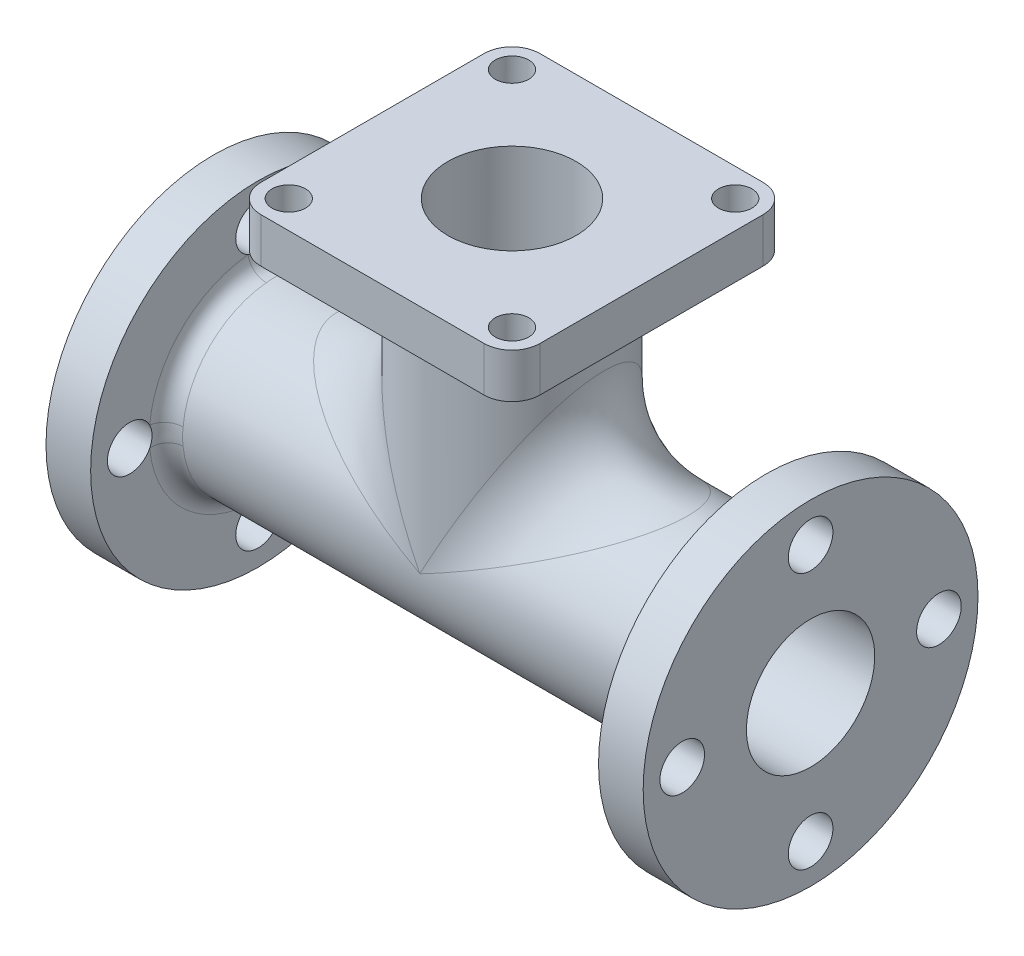
SolidWorks part; units mm, degrees
ref_plane "정면" through (0, 0, 0) normal (0, 0, 1) x (1, 0, 0)
ref_plane "윗면" through (0, 0, 0) normal (0, 1, 0) x (1, 0, 0)
ref_plane "우측면" through (0, 0, 0) normal (1, 0, 0) x (0, 0, -1)
sketch "스케치1" plane through (0, 0, 0) normal (0, 0, 1) x (1, 0, 0)
  line L0 (-60.78, 0) -> (75.4781, 0) construction
  line L1 (-53.5058, 0) -> (-53.5058, 16.5)
  line L2 (-53.5058, 16.5) -> (51.4942, 16.5)
  line L3 (51.4942, 16.5) -> (51.4942, 0)
  line L4 (-53.5058, 0) -> (51.4942, 0)
  dimension "D1" = 105
  dimension "D2" = 16.5
revolve "회전1" add sketch "스케치1" angle 360 about L0
ref_plane "평면4" through (0, 50, 0) normal (0, 1, 0) x (1, 0, 0)
sketch "스케치5" plane through (0, 50, 0) normal (0, 1, 0) x (1, 0, 0)
  circle A0 centre (0, 0) radius 16.5
  dimension "D1" = 33
extrude "보스-돌출2" add sketch "스케치5" against normal up to next
shell "쉘2" thickness 5 removed face at (51.4942, 0, 16.5) removed face at (-53.5058, 0, 16.5) removed face at (0, 50, 16.5)
ref_plane "평면7" through (-53.5058, 0, 0) normal (-1, 0, 0) x (0, 0, 1)
sketch "스케치7" plane through (-53.5058, 0, 0) normal (-1, 0, 0) x (0, 0, 1)
  circle A0 centre (0, 0) radius 30
  circle A1 centre (0, 0) radius 11.5
  dimension "D1" = 60
  dimension "D2" = 23
extrude "보스-돌출4" add sketch "스케치7" against normal blind 8
ref_plane "평면8" through (0, 50, 0) normal (0, 1, 0) x (1, 0, 0)
sketch "스케치8" plane through (0, 50, 0) normal (0, 1, 0) x (1, 0, 0)
  line L1 (-20, 25) -> (20, 25)
  line L2 (-25, 20) -> (-25, -20)
  line L3 (-20, -25) -> (20, -25)
  line L4 (25, 20) -> (25, -20)
  line L5 (-25, 25) -> (25, -25) construction
  line L6 (-25, -25) -> (25, 25) construction
  circle A1 centre (0, 0) radius 11.5
  arc A2 (20, 25) -> (25, 20) centre (20, 20) cw
  arc A3 (25, -20) -> (20, -25) centre (20, -20) cw
  arc A4 (-20, -25) -> (-25, -20) centre (-20, -20) cw
  arc A5 (-20, 25) -> (-25, 20) centre (-20, 20) ccw
  dimension "D1" = 50
  dimension "D2" = 23
  dimension "D4" = 5
  dimension "D3" = 50
extrude "보스-돌출5" add sketch "스케치8" against normal blind 8
sketch "스케치10" plane through (0, 50, 0) normal (0, 1, 0) x (1, 0, 0)
  circle A0 centre (-20, 20) radius 3
  circle A1 centre (-20, -20) radius 3
  circle A2 centre (20, -20) radius 3
  circle A3 centre (20, 20) radius 3
  dimension "D1" = 6
extrude "컷-돌출1" cut sketch "스케치10" against normal through all
ref_plane "평면9" through (-53.5058, 0, 0) normal (-1, 0, 0) x (0, 0, 1)
sketch "스케치11" plane through (-53.5058, 0, 0) normal (-1, 0, 0) x (0, 0, 1)
  circle A2 centre (0, 0) radius 23 construction
  circle A3 centre (0, 23) radius 4
  circle A4 centre (23, 0) radius 4
  circle A5 centre (0, -23) radius 4
  circle A6 centre (-23, 0) radius 4
  dimension "D1" = 46
  dimension "D2" = 8
extrude "컷-돌출2" cut sketch "스케치11" against normal blind 15 contours A3 | A6 | A5 | A4
ref_plane "평면12" through (0, 0, 0) normal (1, 0, 0) x (0, 0, -1)
mirror "대칭 복사7" about plane through (0, 0, 0) normal (1, 0, 0) of "컷-돌출2", "보스-돌출4"
fillet "필렛1" radius 15 2 edges at (-16.5, 16.5, 0) (16.5, 16.5, 0)
fillet "필렛2" radius 3 3 edges at (0, 42, -16.5) (45.5058, 0, -16.5) (-45.5058, 0, 16.5)
